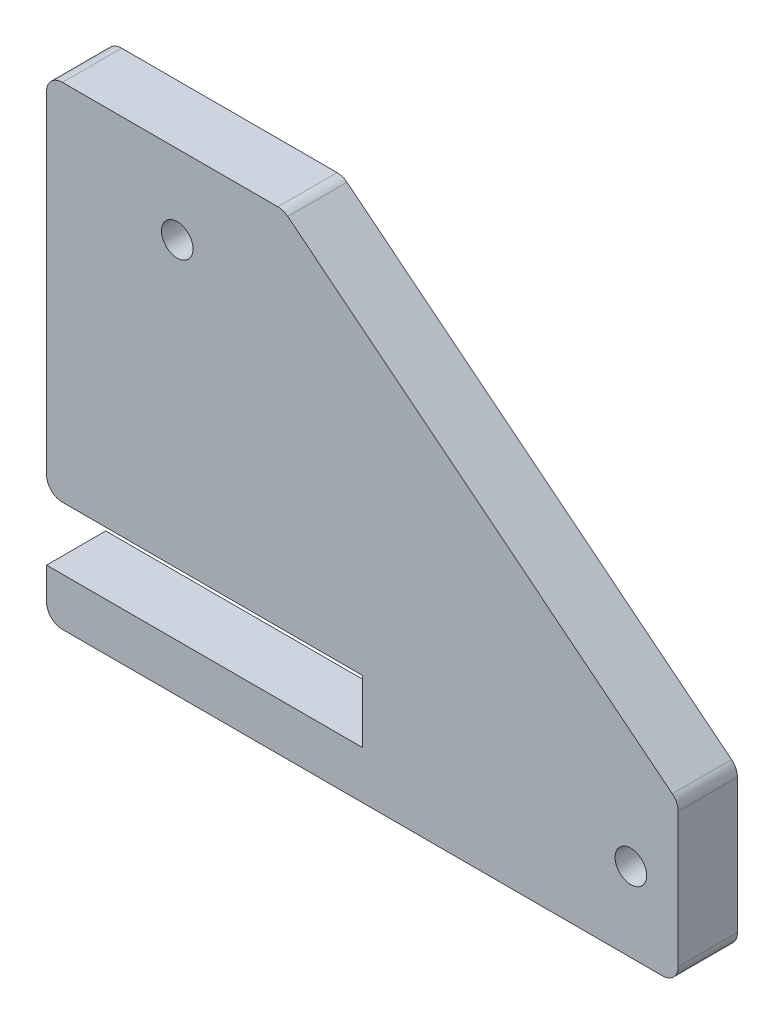
SolidWorks part; units mm, degrees
material "Corrugated Paper"
ref_plane "Front Plane" through (0, 0, 0) normal (0, 0, 1) x (1, 0, 0)
ref_plane "Top Plane" through (0, 0, 0) normal (0, 1, 0) x (1, 0, 0)
ref_plane "Right Plane" through (0, 0, 0) normal (1, 0, 0) x (0, 0, -1)
sketch "Sketch1" plane through (0, 0, 0) normal (0, 0, 1) x (1, 0, 0)
  line L0 (-25.4, 2.5082) -> (-25.4, 6.35)
  line L1 (-25.4, -2.5082) -> (0, -2.5082)
  line L3 (-25.4, 2.5082) -> (0, 2.5082)
  line L4 (0, -2.5082) -> (0, 2.5082)
  line L5 (-25.4, 6.35) -> (25.4, 6.35)
  line L6 (0, 0) -> (25.4, 0) construction
  line L7 (25.4, 6.35) -> (25.4, -6.35)
  line L8 (-25.4, -6.35) -> (25.4, -6.35)
  line L9 (-25.4, -2.5082) -> (-25.4, -6.35)
  line L11 (-25.4, 6.35) -> (25.4, 6.35)
  line L12 (-25.4, 6.35) -> (-25.4, 31.75)
  line L13 (-25.4, 31.75) -> (25.4, 31.75)
  line L14 (25.4, 6.35) -> (25.4, 31.75)
  dimension "D1" = 25.4
  dimension "D2" = 5.0165
  dimension "D3" = 25.4
  dimension "D4" = 12.7
  dimension "D5" = 38.1
extrude "Boss-Extrude1" add sketch "Sketch1" along normal mid plane 4.7625 contours L5 L14 L13 L12 | L6 L4 L1 L9 L8 L7 | L4 L6 L7 L5 L0 L3 region at (3.1255, 3.6477, 0) region at (0, 19.05, 0) region at (3.1255, -3.6477, 0)
sketch "Sketch2" plane through (0, 0, 2.3813) normal (0, 0, 1) x (1, 0, 0)
  line L0 (0, 0) -> (25.4, 0) construction
  line L2 (25.4, -6.35) -> (25.4, 31.75) construction
  circle A0 centre (21.59, 0) radius 1.27
  dimension "D1" = 2.54
  dimension "D2" = 2.54
extrude "Cut-Extrude1" cut sketch "Sketch2" against normal through all
sketch "Sketch3" plane through (0, 0, 2.3813) normal (0, 0, 1) x (1, 0, 0)
  circle A0 centre (-14.888, 25.4) radius 1.27
  circle A1 centre (21.59, 0) radius 1.27 construction
  dimension "D1" = 44.45
  dimension "D2" = 25.4
extrude "Cut-Extrude2" cut sketch "Sketch3" against normal through all
sketch "Sketch4" plane through (0, 0, 2.3813) normal (0, 0, 1) x (1, 0, 0)
  line L0 (-6.35, 31.75) -> (25.4, 6.35)
  line L1 (-25.4, 31.75) -> (25.4, 31.75) construction
  line L2 (25.4, -6.35) -> (25.4, 31.75) construction
  line L3 (-6.35, 31.75) -> (25.4, 31.75)
  line L4 (25.4, 31.75) -> (25.4, 6.35)
  dimension "D1" = 25.4
  dimension "D2" = 31.75
extrude "Cut-Extrude3" cut sketch "Sketch4" against normal through all
fillet "Fillet1" radius 1.27 6 edges at (-25.4, -6.35, 0) (25.4, -6.35, 0) (-25.4, 2.5082, 0) (-25.4, 31.75, 0) (25.4, 6.35, 0) (-6.35, 31.75, 0)
equation "\"D2@Sketch1\"=\"thick\"+\"clear\""
equation "\"D1@Sketch2\" = \"rodThick\""
equation "\"D1@Boss-Extrude1\" = \"thick\""
equation "\"rodThick\"= 0.1in"
equation "\"thick\"= 3/16in"
equation "\"clear\"= 0.01in"
